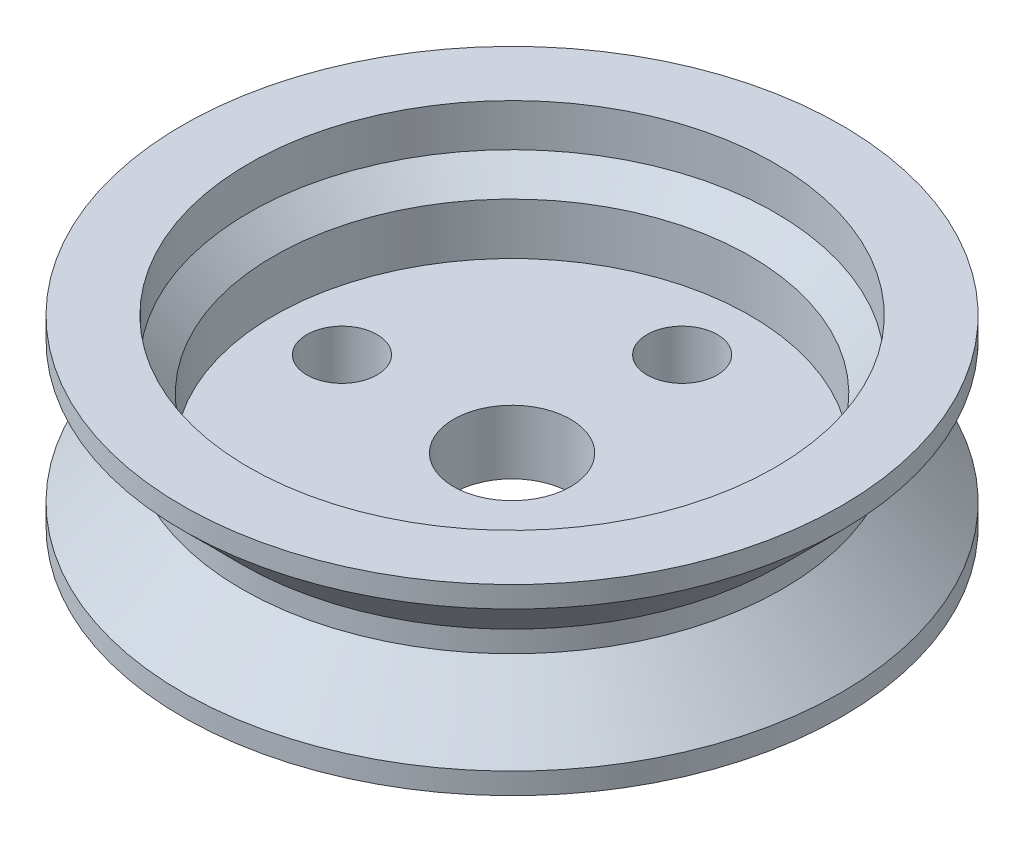
SolidWorks part; units mm, degrees
ref_plane "前视基准面" through (0, 0, 0) normal (0, 0, 1) x (1, 0, 0)
ref_plane "上视基准面" through (0, 0, 0) normal (0, 1, 0) x (1, 0, 0)
ref_plane "右视基准面" through (0, 0, 0) normal (1, 0, 0) x (0, 0, -1)
sketch "草图2" plane through (0, 0, 0) normal (0, 0, 1) x (1, 0, 0)
  line L0 (0, 0) -> (-15.5, 0)
  line L1 (-15.5, 0) -> (-15.5, 1)
  line L2 (-15.5, 1) -> (-12.7, 3.8)
  line L3 (-12.7, 3.8) -> (-12.7, 4.8)
  line L4 (-12.7, 4.8) -> (-15.5, 7.6)
  line L5 (-15.5, 7.6) -> (-15.5, 8.6)
  line L6 (-15.5, 8.6) -> (-12.3787, 8.6)
  line L11 (-11.2, 5.4213) -> (-12.3787, 6.6)
  line L12 (-12.3787, 6.6) -> (-12.3787, 8.6)
  line L15 (0, 0) -> (0, 1.5)
  line L16 (-12.7, 4.3) -> (-18.965, 4.3) construction
  line L18 (-11.2, 3) -> (-11.2, 5.4213)
  line L19 (-11.2, 3) -> (0, 3)
  line L20 (0, 3) -> (0, 1.5)
  dimension "D2" = 1.5
  dimension "D3" = 1.5
  dimension "D4" = 11.2
  dimension "D5" = 1
  dimension "D6" = 1
  dimension "D7" = 15.5
  dimension "D8" = 3
  dimension "D9" = 1
  dimension "D10" = 45
  dimension "D11" = 2
  dimension "D12" = 12.7
revolve "旋转1" add sketch "草图2" angle 360 about L15
ref_axis "基准轴1" through (0, 8.6, 0) along (0, -1, 0)
sketch "草图3" plane through (0, 0, 0) normal (0, -1, 0) x (1, 0, 0)
  circle A0 centre (0, 0) radius 2.75
  circle A1 centre (0, 8) radius 1.65
  circle A2 centre (8, 0) radius 1.65
  circle A3 centre (0, -8) radius 1.65
  circle A4 centre (-8, 0) radius 1.65
  point P14 (0, 0)
  dimension "D1" = 5.5
  dimension "D2" = 3.3
  dimension "D3" = 8
  dimension "D4" = 4
extrude "切除-拉伸1" cut sketch "草图3" against normal through all contours A1 | A4 | A3 | A2 | A0
